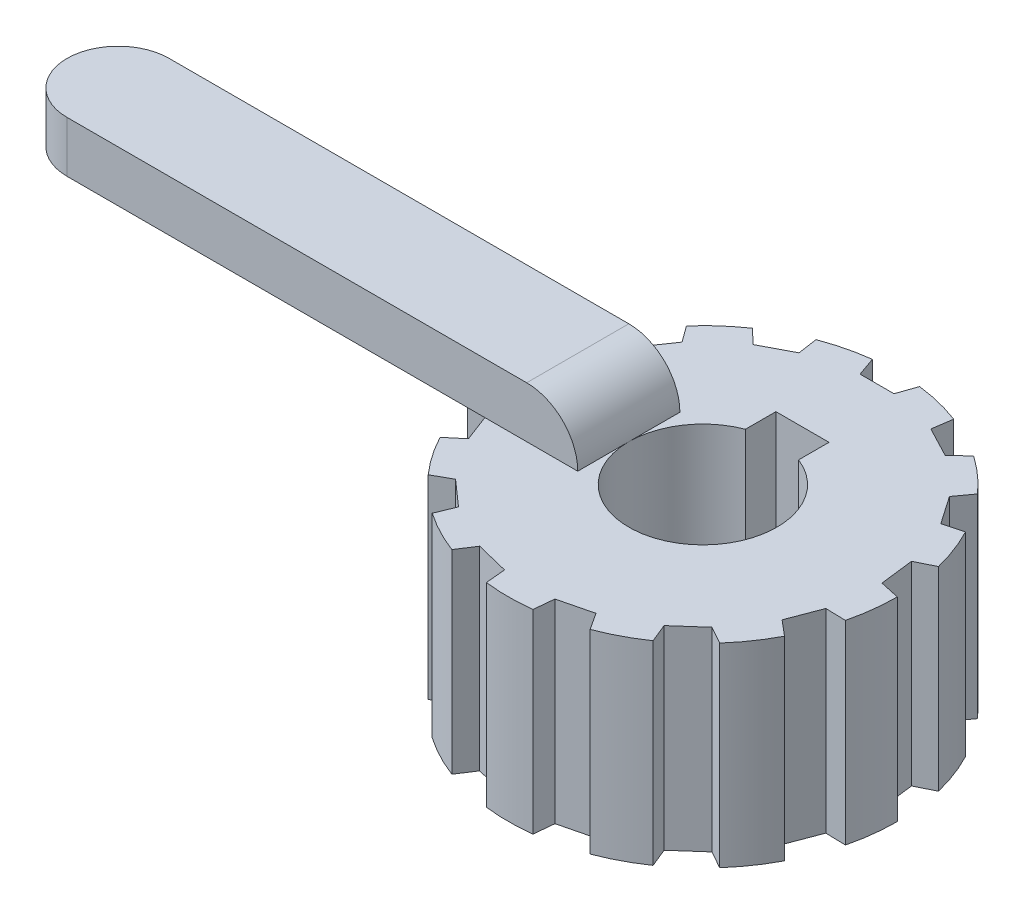
SolidWorks part; units mm, degrees
ref_plane "Front Plane" through (0, 0, 0) normal (0, 0, 1) x (1, 0, 0)
ref_plane "Top Plane" through (0, 0, 0) normal (0, 1, 0) x (1, 0, 0)
ref_plane "Right Plane" through (0, 0, 0) normal (1, 0, 0) x (0, 0, -1)
sketch "Sketch5" plane through (0, 0, 0) normal (0, 1, 0) x (1, 0, 0)
  circle A0 centre (0, 0) radius 19.05
extrude "Boss-Extrude2" add sketch "Sketch5" along normal blind 19.05
sketch "Sketch8" plane through (0, 19.05, 0) normal (0, 1, 0) x (1, 0, 0)
  line L0 (0, 19.05) -> (2.36, 19.05)
  line L1 (0, 19.05) -> (-2.36, 19.05)
  line L5 (0, 17.05) -> (-1.66, 17.05)
  line L6 (0, 17.05) -> (1.66, 17.05)
  line L7 (-2.36, 19.05) -> (-1.66, 17.05)
  line L8 (2.36, 19.05) -> (1.66, 17.05)
  circle A0 centre (0, 0) radius 19.05 construction
  point P0 (0, 19.05)
  point P2 (0, 20.32)
  dimension "D1" = 1.66
  dimension "D2" = 1.66
  dimension "D3" = 2
  dimension "D4" = 2.36
  dimension "D5" = 2.36
extrude "Cut-Extrude1" cut sketch "Sketch8" against normal blind 22.05
pattern_circular "CirPattern1" count 13 over 360 about axis through (0, 19.05, 0) along (0, 1, 0) of "Cut-Extrude1"
sketch "Sketch9" plane through (0, 19.05, 0) normal (0, 1, 0) x (1, 0, 0)
  line L0 (0, 7.25) -> (2.6, 7.25)
  line L1 (0, 7.25) -> (-2.6, 7.25)
  line L2 (-2.6, 7.25) -> (-2.6, 6.7678)
  line L3 (2.6, 7.25) -> (2.6, 6.7678)
  line L4 (-2.6, 7.25) -> (-2.6, 9.75)
  line L5 (-2.6, 9.75) -> (2.6, 9.75)
  line L6 (2.6, 9.75) -> (2.6, 7.25)
  circle A0 centre (0, 0) radius 7.25
extrude "Cut-Extrude2" cut sketch "Sketch9" against normal blind 25.4 contours A0 | L6 L5 L4 L1 L0 | A0 L1 L2 | A0 L3 L0 region at (0, 19.05, -8.5) region at (-1.9544, 19.05, -7.1062) region at (1.9544, 19.05, -7.1062) region at (0, 19.05, 0)
sketch "Sketch10" plane through (0, 19.05, 0) normal (0, 1, 0) x (1, 0, 0)
  line L7 (-7.25, 0) -> (-7.25, 5)
  line L8 (-7.25, 0) -> (-7.25, -5)
  line L9 (-7.25, 5) -> (-57.25, 5)
  line L10 (-57.25, 5) -> (-57.25, -5)
  line L11 (-57.25, -5) -> (-7.25, -5)
  arc A2 (-57.25, 5) -> (-57.25, -5) centre (-57.25, 0) ccw
  arc A3 (-2.6, 6.7678) -> (2.6, 6.7678) centre (0, 0) ccw construction
  point P0 (-7.25, 0)
  dimension "D1" = 50
  dimension "D2" = 5
  dimension "D3" = 5
extrude "Boss-Extrude4" add sketch "Sketch10" along normal blind 5 contours L10 A2 | L10 L11 L8 L7 L9 region at (-32.25, 19.05, 0) region at (-59.3721, 19.05, 0)
fillet "Fillet2" radius 5 1 edges at (-7.25, 24.05, 0)
